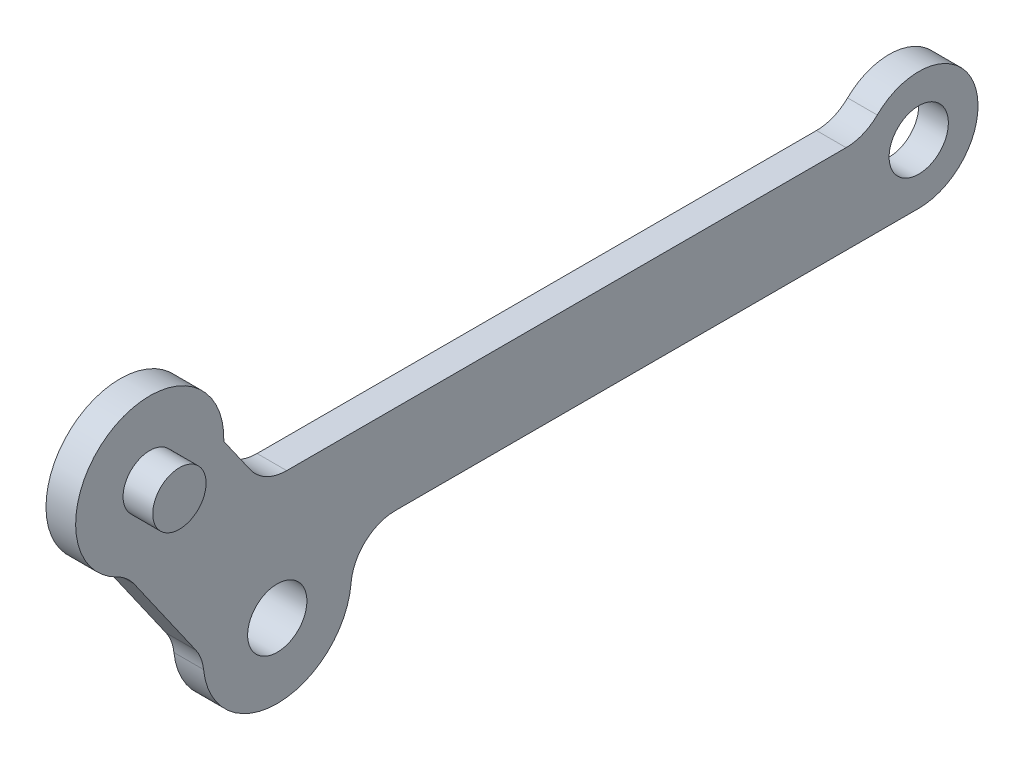
SolidWorks part; units mm, degrees
ref_plane "前视基准面" through (0, 0, 0) normal (0, 0, 1) x (1, 0, 0)
ref_plane "上视基准面" through (0, 0, 0) normal (0, 1, 0) x (1, 0, 0)
ref_plane "右视基准面" through (0, 0, 0) normal (1, 0, 0) x (0, 0, -1)
other "Configuration Table"
sketch "草图1" plane through (0, 0, 0) normal (1, 0, 0) x (0, 0, -1)
  line L1 (0, 0) -> (44.2012, 0)
  line L2 (0, 0) -> (4.2012, -6)
  line L3 (4.2012, -6) -> (44.2012, -6)
  line L4 (44.2012, 0) -> (44.2012, -6)
  line L5 (-10.9556, 1.6987) -> (-4.4024, 6.2873)
  line L6 (-10.9556, 1.6987) -> (-2.352, -10.5886)
  line L7 (-2.352, -10.5886) -> (4.2012, -6)
  line L8 (-4.4024, 6.2873) -> (4.2012, -6)
  circle A0 centre (-7.679, 3.993) radius 5
  circle A1 centre (0.9246, -8.2943) radius 5
  circle A3 centre (44.2012, -2) radius 4
  circle A4 centre (-7.679, 3.993) radius 2
  circle A5 centre (44.2012, -2) radius 2
  circle A6 centre (0.9246, -8.2943) radius 2
  circle A7 centre (0.9246, -8.2943) radius 3
  dimension "D5" = 10
  dimension "D6" = 10
  dimension "D8" = 8
  dimension "D9" = 4
  dimension "D10" = 6
  dimension "D1" = 125
  dimension "D2" = 40
  dimension "D3" = 6
  dimension "D4" = 8
  dimension "D7" = 15
extrude "凸台-拉伸1" add sketch "草图1" along normal blind 2 contours A3 L1 L2 A1 L3 | A0 | L8 L5 L6 L7 | A1 | A3 region at (0, -2.9524, -21.636)
extrude "凸台-拉伸2" add sketch "草图1<4>" against normal blind 2 contours A7
sketch "草图1<4>" plane through (0, 0, 0) normal (1, 0, 0) x (0, 0, -1) same geometry as "草图1"
extrude "切除-拉伸1" cut sketch "草图1<3>" along normal through all both and the other way through all contours A4 | A6 | A5
sketch "草图1<3>" plane through (0, 0, 0) normal (1, 0, 0) x (0, 0, -1) same geometry as "草图1"
fillet "圆角1" radius 3 5 edges at (1, 0, -40.7371) (1, -8.1312, 4.0727) (1, -0.7588, 9.2349) (1, -6, -5.3672) (1, 0, 0)
sketch "草图2" plane through (2, 0, 0) normal (1, 0, 0) x (0, 0, -1)
  circle A0 centre (-7.679, 3.993) radius 2
  circle A1 centre (-7.679, 3.993) radius 1.8
  circle A2 centre (-7.679, 3.993) radius 2 construction
  dimension "D1" = 3.6
extrude "凸台-拉伸3" add sketch "草图2" against normal up to surface (2 mm away) contours A0 up to face at (0, 3.993, 5.679)
extrude "凸台-拉伸4" add sketch "草图2<3>" along normal blind 2 contours A1 region at (2, 3.993, 7.679)
sketch "草图2<3>" plane through (2, 0, 0) normal (1, 0, 0) x (0, 0, -1) same geometry as "草图2"
